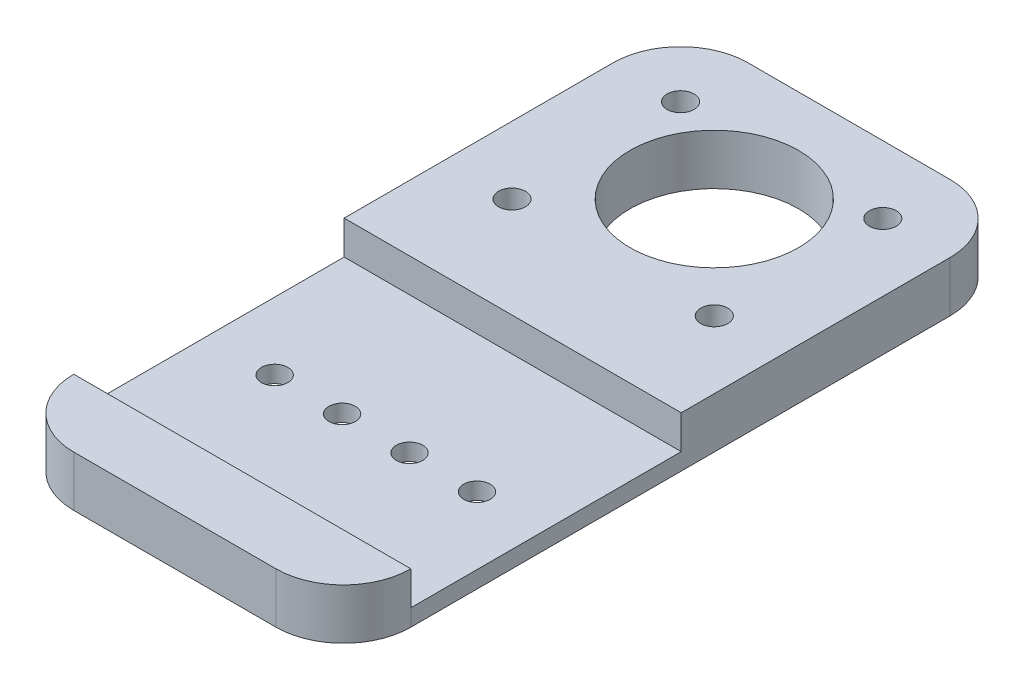
SolidWorks part; units mm, degrees
ref_plane "Front Plane" through (0, 0, 0) normal (0, 0, 1) x (1, 0, 0)
ref_plane "Top Plane" through (0, 0, 0) normal (0, 1, 0) x (1, 0, 0)
ref_plane "Right Plane" through (0, 0, 0) normal (1, 0, 0) x (0, 0, -1)
sketch "Sketch1" plane through (0, 0, 0) normal (0, 1, 0) x (1, 0, 0)
  line L0 (0, -111.3091) -> (63.5, -111.3091)
  line L1 (0, 2.9909) -> (63.5, 2.9909)
  line L2 (0, 2.9909) -> (0, -124.0091)
  line L3 (0, -124.0091) -> (63.5, -124.0091)
  line L4 (63.5, 2.9909) -> (63.5, -124.0091)
  line L7 (0, -60.3821) -> (63.5, -60.3821)
  circle A0 centre (31.75, -22.4091) radius 15.875
  circle A1 centre (12.7, -86.1631) radius 2.4892
  circle A2 centre (25.4, -86.1631) radius 2.4892
  circle A3 centre (38.1, -86.1631) radius 2.4892
  circle A4 centre (50.8, -86.1631) radius 2.4892
  dimension "D3" = 31.75
  dimension "D4" = 25.4
  dimension "D5" = 31.75
  dimension "D6" = 4.9784
  dimension "D7" = 12.7
  dimension "D8" = 37.846
  dimension "D1" = 63.5
  dimension "D2" = 127
  dimension "D10" = 12.7
  dimension "D12" = 63.627
  dimension "D9" = 4
extrude "Boss-Extrude2" add sketch "Sketch1" along normal blind 9.525 contours L4 L0 L2 L3 | L2 L7 L4 L1 A0 region at (31.75, 0, 117.6591) region at (0.8971, 0, 28.6956)
extrude "Boss-Extrude3" add sketch "Sketch1<3>" along normal blind 3.175 contours L7 L2 L0 L4 A4 A3 A2 A1 region at (31.75, 0, 85.8377)
sketch "Sketch1<3>" plane through (0, 0, 0) normal (0, 1, 0) x (1, 0, 0) same geometry as "Sketch1"
fillet "Fillet2" radius 12.7 4 edges at (0, 4.7625, 124.0091) (63.5, 4.7625, 124.0091) (0, 4.7625, -2.9909) (63.5, 4.7625, -2.9909)
sketch "Sketch2" plane through (0, 0, 0) normal (0, -1, 0) x (1, 0, 0)
  circle A0 centre (12.7, 41.4591) radius 2.54
  circle A1 centre (50.8, 41.4591) radius 2.54
  circle A2 centre (50.8, 9.7091) radius 2.54
  circle A3 centre (12.7, 9.7091) radius 2.54
  arc A8 (0, 9.7091) -> (12.7, -2.9909) centre (12.7, 9.7091) ccw construction
  arc A9 (50.8, -2.9909) -> (63.5, 9.7091) centre (50.8, 9.7091) ccw construction
  dimension "D1" = 5.08
  dimension "D2" = 31.75
extrude "Cut-Extrude1" cut sketch "Sketch2" against normal through all
